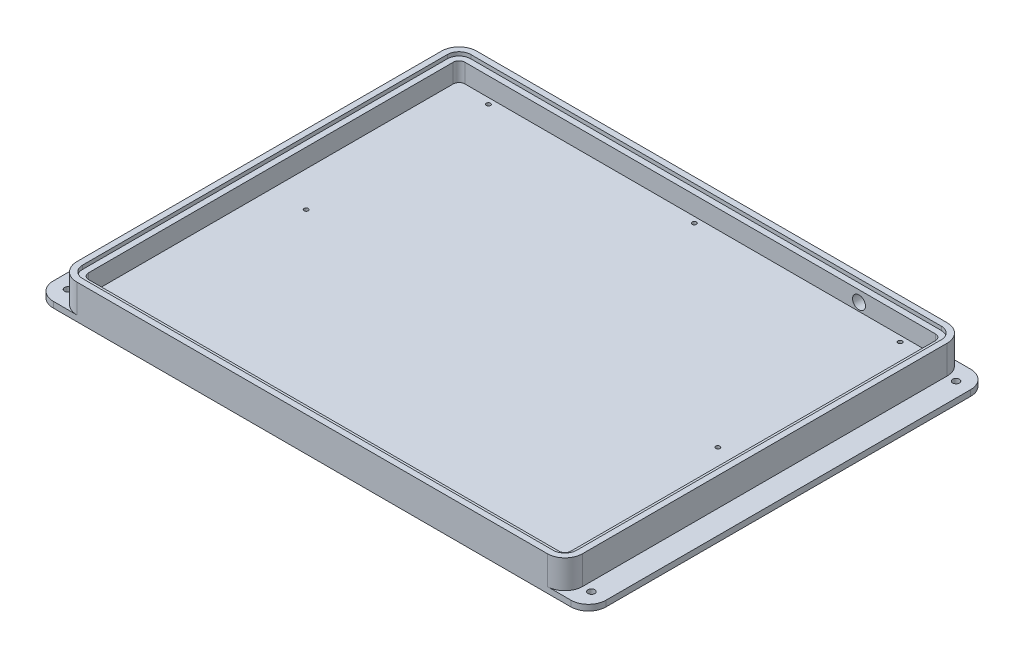
SolidWorks part; units mm, degrees
ref_plane "Front Plane" through (0, 0, 0) normal (0, 0, 1) x (1, 0, 0)
ref_plane "Top Plane" through (0, 0, 0) normal (0, 1, 0) x (1, 0, 0)
ref_plane "Right Plane" through (0, 0, 0) normal (1, 0, 0) x (0, 0, -1)
sketch "Sketch1" plane through (0, 0, 0) normal (0, 1, 0) x (1, 0, 0)
  line L1 (0, 0) -> (273.05, 0)
  line L2 (0, 0) -> (0, 215.9)
  line L3 (0, 215.9) -> (273.05, 215.9)
  line L4 (273.05, 0) -> (273.05, 215.9)
  dimension "D1" = 273.05
  dimension "D2" = 215.9
extrude "Boss-Extrude1" add sketch "Sketch1" along normal blind 18.542
sketch "Sketch7" plane through (0, 0, 0) normal (0, -1, 0) x (1, 0, 0)
  line L0 (273.05, -215.9) -> (0, -215.9) construction
  line L1 (-3.175, 0) -> (276.225, 0)
  line L2 (-12.7, -9.525) -> (-12.7, -206.375)
  line L3 (-3.175, -215.9) -> (276.225, -215.9)
  line L4 (285.75, -9.525) -> (285.75, -206.375)
  line L5 (0, 0) -> (273.05, 0) construction
  line L6 (0, -215.9) -> (0, 0) construction
  line L7 (273.05, 0) -> (273.05, -215.9) construction
  arc A0 (-12.7, -206.375) -> (-3.175, -215.9) centre (-3.175, -206.375) ccw
  arc A1 (276.225, -215.9) -> (285.75, -206.375) centre (276.225, -206.375) ccw
  arc A2 (276.225, 0) -> (285.75, -9.525) centre (276.225, -9.525) cw
  arc A3 (-3.175, 0) -> (-12.7, -9.525) centre (-3.175, -9.525) ccw
  dimension "D3" = 9.525
  dimension "D1" = 12.7
  dimension "D2" = 12.7
extrude "Boss-Extrude2" add sketch "Sketch7" against normal blind 3.175
fillet "Fillet1" radius 9.525 4 edges at (273.05, 10.8585, 0) (273.05, 10.8585, -215.9) (0, 10.8585, 0) (0, 10.8585, -215.9)
sketch "Sketch3" plane through (0, 18.542, 0) normal (0, 1, 0) x (1, 0, 0)
  line L25 (266.7, 9.525) -> (266.7, 206.375)
  line L26 (9.525, 6.35) -> (263.525, 6.35)
  line L27 (6.35, 206.375) -> (6.35, 9.525)
  line L28 (263.525, 209.55) -> (9.525, 209.55)
  line L29 (266.7, 9.525) -> (266.7, 206.375)
  line L30 (9.525, 6.35) -> (263.525, 6.35)
  line L31 (6.35, 206.375) -> (6.35, 9.525)
  line L32 (263.525, 209.55) -> (9.525, 209.55)
  arc A21 (266.7, 206.375) -> (263.525, 209.55) centre (263.525, 206.375) ccw
  arc A22 (263.525, 6.35) -> (266.7, 9.525) centre (263.525, 9.525) ccw
  arc A23 (6.35, 9.525) -> (9.525, 6.35) centre (9.525, 9.525) ccw
  arc A24 (9.525, 209.55) -> (6.35, 206.375) centre (9.525, 206.375) ccw
  arc A25 (266.7, 206.375) -> (263.525, 209.55) centre (263.525, 206.375) ccw
  arc A26 (263.525, 6.35) -> (266.7, 9.525) centre (263.525, 9.525) ccw
  arc A27 (6.35, 9.525) -> (9.525, 6.35) centre (9.525, 9.525) ccw
  arc A28 (9.525, 209.55) -> (6.35, 206.375) centre (9.525, 206.375) ccw
  dimension "D1" = 6.35
extrude "Cut-Extrude1" cut sketch "Sketch3" against normal blind 12.192
sketch "Sketch4" plane through (0, 18.542, 0) normal (0, 1, 0) x (1, 0, 0)
  line L24 (269.875, 9.525) -> (269.875, 206.375)
  line L25 (9.525, 3.175) -> (263.525, 3.175)
  line L26 (3.175, 206.375) -> (3.175, 9.525)
  line L27 (263.525, 212.725) -> (9.525, 212.725)
  line L28 (269.875, 9.525) -> (269.875, 206.375)
  line L29 (9.525, 3.175) -> (263.525, 3.175)
  line L30 (3.175, 206.375) -> (3.175, 9.525)
  line L31 (263.525, 212.725) -> (9.525, 212.725)
  arc A20 (269.875, 206.375) -> (263.525, 212.725) centre (263.525, 206.375) ccw
  arc A21 (263.525, 3.175) -> (269.875, 9.525) centre (263.525, 9.525) ccw
  arc A22 (3.175, 9.525) -> (9.525, 3.175) centre (9.525, 9.525) ccw
  arc A23 (9.525, 212.725) -> (3.175, 206.375) centre (9.525, 206.375) ccw
  arc A24 (269.875, 206.375) -> (263.525, 212.725) centre (263.525, 206.375) ccw
  arc A25 (263.525, 3.175) -> (269.875, 9.525) centre (263.525, 9.525) ccw
  arc A26 (3.175, 9.525) -> (9.525, 3.175) centre (9.525, 9.525) ccw
  arc A27 (9.525, 212.725) -> (3.175, 206.375) centre (9.525, 206.375) ccw
  dimension "D1" = 3.175
extrude "Cut-Extrude2" cut sketch "Sketch4" against normal blind 2.032
sketch "Sketch5" plane through (0, 6.35, 0) normal (0, 1, 0) x (1, 0, 0)
  line L0 (136.525, 206.375) -> (136.525, 209.55) construction
  line L1 (25.4, 206.375) -> (247.65, 206.375) construction
  line L2 (25.4, 206.375) -> (25.4, 9.525) construction
  line L3 (25.4, 9.525) -> (247.65, 9.525) construction
  line L4 (247.65, 206.375) -> (247.65, 9.525) construction
  line L5 (263.525, 209.55) -> (9.525, 209.55) construction
  line L6 (25.4, 107.95) -> (6.35, 107.95) construction
  line L7 (6.35, 206.375) -> (6.35, 9.525) construction
  line L8 (247.65, 107.95) -> (266.7, 107.95) construction
  line L9 (266.7, 9.525) -> (266.7, 206.375) construction
  line L10 (136.525, 9.525) -> (136.525, 6.35) construction
  line L11 (263.525, 6.35) -> (9.525, 6.35) construction
  circle A0 centre (25.4, 206.375) radius 1.1303
  circle A1 centre (136.525, 206.375) radius 1.1303
  circle A2 centre (247.65, 206.375) radius 1.1303
  circle A3 centre (247.65, 107.95) radius 1.1303
  circle A4 centre (25.4, 107.95) radius 1.1303
  circle A5 centre (25.4, 9.525) radius 1.1303
  circle A6 centre (136.525, 9.525) radius 1.1303
  circle A7 centre (247.65, 9.525) radius 1.1303
  dimension "D3" = 2.2606
  dimension "D1" = 196.85
  dimension "D2" = 222.25
extrude "Cut-Extrude3" cut sketch "Sketch5" against normal blind 4.7625
sketch "Sketch6" plane through (0, 0, -215.9) normal (0, 0, -1) x (-1, 0, 0)
  line L1 (-273.05, 3.175) -> (-273.05, 18.542) construction
  line L3 (-263.525, 18.542) -> (-9.525, 18.542) construction
  circle A0 centre (-222.25, 10.6045) radius 3.4925
  dimension "D2" = 6.985
  dimension "D1" = 50.8
  dimension "D3" = 7.9375
extrude "Cut-Extrude4" cut sketch "Sketch6" against normal blind 12.7
sketch "Sketch8" plane through (0, 3.175, 0) normal (0, 1, 0) x (1, 0, 0)
  line L0 (-4.7625, 215.9) -> (-4.7625, 0) construction
  line L1 (-12.7, 9.525) -> (-12.7, 206.375) construction
  line L2 (-3.175, 215.9) -> (9.525, 215.9) construction
  line L3 (285.75, 206.375) -> (285.75, 9.525) construction
  line L4 (-4.7625, 206.375) -> (277.8125, 206.375) construction
  line L5 (-4.7625, 206.375) -> (-4.7625, 9.525) construction
  line L6 (-4.7625, 9.525) -> (277.8125, 9.525) construction
  line L7 (277.8125, 206.375) -> (277.8125, 9.525) construction
  line L8 (9.525, 0) -> (-3.175, 0) construction
  circle A0 centre (-4.7625, 206.375) radius 1.8288
  circle A1 centre (-4.7625, 9.525) radius 1.8288
  circle A2 centre (277.8125, 9.525) radius 1.8288
  circle A3 centre (277.8125, 206.375) radius 1.8288
  dimension "D2" = 3.6576
  dimension "D1" = 7.9375
  dimension "D3" = 9.525
  dimension "D4" = 7.9375
  dimension "D5" = 9.525
extrude "Cut-Extrude5" cut sketch "Sketch8" against normal through all
